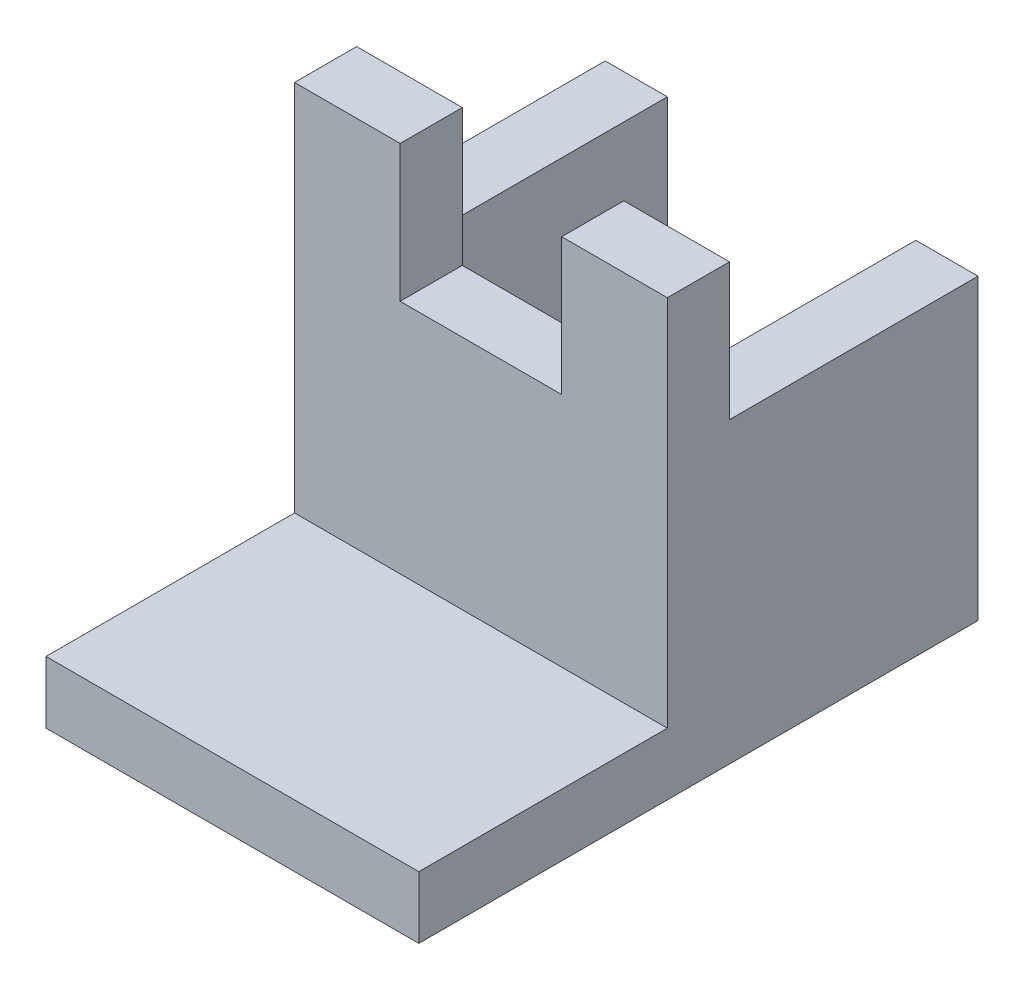
SolidWorks part; units mm, degrees
ref_plane "Front Plane" through (0, 0, 0) normal (0, 0, 1) x (1, 0, 0)
ref_plane "Top Plane" through (0, 0, 0) normal (0, 1, 0) x (1, 0, 0)
ref_plane "Right Plane" through (0, 0, 0) normal (1, 0, 0) x (0, 0, -1)
sketch "Sketch1" plane through (0, 0, 0) normal (0, 1, 0) x (1, 0, 0)
  line L1 (0, 0) -> (30, 0)
  line L2 (0, 0) -> (0, 45)
  line L3 (0, 45) -> (30, 45)
  line L4 (30, 0) -> (30, 45)
  dimension "D1" = 30
  dimension "D2" = 45
extrude "Boss-Extrude1" add sketch "Sketch1" along normal blind 5
sketch "Sketch2" plane through (0, 5, 0) normal (0, 1, 0) x (1, 0, 0)
  line L11 (0, 45) -> (0, 0) construction
  line L12 (0, 25) -> (30, 25)
  line L13 (0, 25) -> (0, 20)
  line L14 (0, 20) -> (30, 20)
  line L15 (30, 25) -> (30, 20)
  line L16 (30, 0) -> (30, 45) construction
  line L17 (30, 45) -> (0, 45) construction
  dimension "D1" = 5
  dimension "D2" = 20
extrude "Boss-Extrude2" add sketch "Sketch2" along normal blind 30
sketch "Sketch3" plane through (0, 5, 0) normal (0, 1, 0) x (1, 0, 0)
  line L1 (0, 25) -> (5, 25)
  line L2 (0, 25) -> (0, 45)
  line L3 (0, 45) -> (5, 45)
  line L4 (5, 25) -> (5, 45)
  line L5 (30, 45) -> (0, 45) construction
  line L6 (0, 45) -> (0, 25) construction
  line L7 (25, 45) -> (30, 45)
  line L8 (25, 45) -> (25, 25)
  line L9 (25, 25) -> (30, 25)
  line L10 (30, 45) -> (30, 25)
  line L11 (0, 25) -> (30, 25) construction
  dimension "D1" = 5
  dimension "D2" = 5
  dimension "D3" = 20
  dimension "D4" = 0
extrude "Boss-Extrude3" add sketch "Sketch3" along normal blind 19
sketch "Sketch4" plane through (0, 35, 0) normal (0, 1, 0) x (1, 0, 0)
  line L0 (0, 20) -> (30, 20) construction
  line L1 (8.5, 20) -> (21.5, 20)
  line L2 (8.5, 20) -> (8.5, 25)
  line L3 (8.5, 25) -> (21.5, 25)
  line L4 (21.5, 20) -> (21.5, 25)
  line L5 (0, 25) -> (30, 25) construction
  line L6 (0, 25) -> (0, 20) construction
  point P8 (0, 0)
  dimension "D1" = 13
  dimension "D2" = 8.5
extrude "Cut-Extrude1" cut sketch "Sketch4" against normal blind 11
